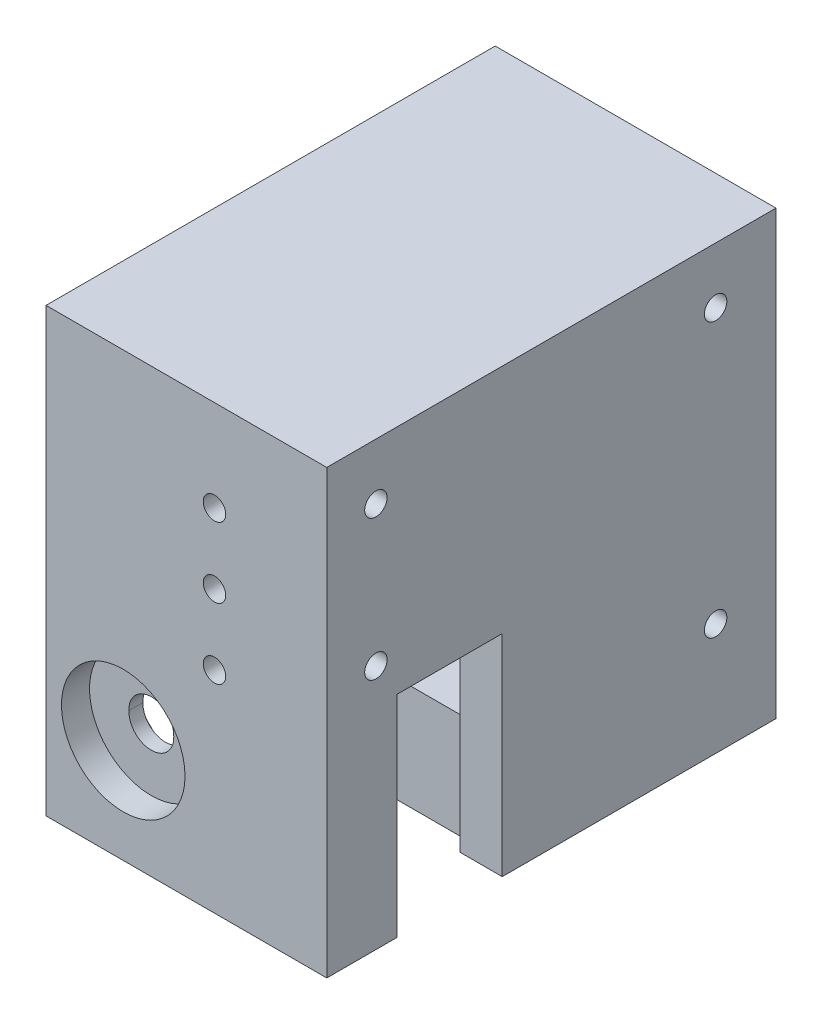
SolidWorks part; units mm, degrees
ref_plane "Front Plane" through (0, 0, 0) normal (0, 0, 1) x (1, 0, 0)
ref_plane "Top Plane" through (0, 0, 0) normal (0, 1, 0) x (1, 0, 0)
ref_plane "Right Plane" through (0, 0, 0) normal (1, 0, 0) x (0, 0, -1)
sketch "Sketch1" plane through (0, 0, 0) normal (0, 0, 1) x (1, 0, 0)
  line L1 (-1.5468, -4.5791) -> (49.2532, -4.5791)
  line L2 (-1.5468, -4.5791) -> (-1.5468, -80.7791)
  line L3 (-1.5468, -80.7791) -> (49.2532, -80.7791)
  line L4 (49.2532, -4.5791) -> (49.2532, -80.7791)
  dimension "D1" = 50.8
  dimension "D2" = 76.2
extrude "Boss-Extrude1" add sketch "Sketch1" along normal blind 12.7
sketch "Sketch3" plane through (0, 0, 12.7) normal (0, 0, 1) x (1, 0, 0)
  line L0 (49.2532, -80.7791) -> (49.2532, -4.5791) construction
  line L1 (49.2532, -4.5791) -> (-1.5468, -4.5791) construction
  line L2 (28.9332, -4.5791) -> (28.9332, -80.7791) construction
  line L4 (-1.5468, -80.7791) -> (49.2532, -80.7791) construction
  circle A0 centre (28.9332, -42.6791) radius 2.032
  circle A1 centre (28.9332, -29.9791) radius 2.032
  circle A2 centre (28.9332, -17.2791) radius 2.032
  dimension "D1" = 12.7
  dimension "D2" = 4.064
  dimension "D3" = 4.064
  dimension "D4" = 4.064
  dimension "D9" = 12.7
  dimension "D5" = 0
  dimension "D6" = 12.7
  dimension "D7" = 20.32
  dimension "D8" = 0
extrude "Cut-Extrude1" cut sketch "Sketch3" against normal blind 12.7
sketch "Sketch4" plane through (0, 0, 12.7) normal (0, 0, 1) x (1, 0, 0)
  circle A1 centre (12.4232, -61.9814) radius 4.064
  circle A4 centre (28.9332, -42.6791) radius 2.032 construction
  dimension "D1" = 25.4
  dimension "D2" = 8.128
  dimension "D3" = 16.51
sketch "Sketch17" plane through (0, 0, 0) normal (0, 0, -1) x (-1, 0, 0)
  line L0 (1.5468, -80.7791) -> (-49.2532, -80.7791) construction
  line L1 (-49.2532, -4.5791) -> (-41.6332, -4.5791)
  line L2 (-49.2532, -4.5791) -> (-49.2532, -80.7791)
  line L3 (-49.2532, -80.7791) -> (-41.6332, -80.7791)
  line L4 (-41.6332, -4.5791) -> (-41.6332, -80.7791)
  dimension "D1" = 7.62
extrude "Boss-Extrude13" add sketch "Sketch17" along normal blind 68.58
sketch "Sketch18" plane through (41.6332, 0, 0) normal (-1, 0, 0) x (0, 0, 1)
  line L1 (-68.58, -80.7791) -> (-64.77, -80.7791)
  line L2 (-68.58, -80.7791) -> (-68.58, -61.7291)
  line L3 (-68.58, -61.7291) -> (-64.77, -61.7291)
  line L4 (-64.77, -80.7791) -> (-64.77, -61.7291)
  dimension "D1" = 19.05
  dimension "D2" = 3.81
extrude "Boss-Extrude14" add sketch "Sketch18" along normal blind 43.18
sketch "Sketch19" plane through (41.6332, 0, 0) normal (-1, 0, 0) x (0, 0, 1)
  line L0 (-64.77, -80.7791) -> (0, -80.7791) construction
  line L1 (-21.59, -80.7791) -> (-50.8, -80.7791)
  line L2 (-21.59, -80.7791) -> (-21.59, -61.7291)
  line L3 (-21.59, -61.7291) -> (-50.8, -61.7291)
  line L4 (-50.8, -80.7791) -> (-50.8, -61.7291)
  line L5 (-64.77, -80.7791) -> (-64.77, -61.7291) construction
  dimension "D1" = 13.97
  dimension "D2" = 29.21
  dimension "D3" = 19.05
extrude "Boss-Extrude15" add sketch "Sketch19" along normal blind 43.18
extrude "Cut-Extrude5" cut sketch "Sketch4" against normal through all contours A1
sketch "Sketch21" plane through (0, 0, 0) normal (0, 0, -1) x (-1, 0, 0)
  circle A0 centre (-12.4232, -61.9814) radius 11.176
  circle A1 centre (-12.4232, -61.9814) radius 4.064
  dimension "D1" = 22.352
  dimension "D2" = 8.128
extrude "Cut-Extrude6" cut sketch "Sketch21" against normal blind 5.08
sketch "Sketch22" plane through (0, 0, 12.7) normal (0, 0, 1) x (1, 0, 0)
  circle A0 centre (12.4232, -61.9814) radius 11.176
  circle A1 centre (12.4232, -61.9814) radius 4.064
  dimension "D1" = 22.352
  dimension "D2" = 8.128
extrude "Cut-Extrude7" cut sketch "Sketch22" against normal blind 5.08
sketch "Sketch23" plane through (41.6332, 0, 0) normal (-1, 0, 0) x (0, 0, 1)
  line L1 (0, -80.7791) -> (-19.05, -80.7791)
  line L2 (0, -80.7791) -> (0, -42.6791)
  line L3 (0, -42.6791) -> (-19.05, -42.6791)
  line L4 (-19.05, -80.7791) -> (-19.05, -42.6791)
  dimension "D1" = 38.1
  dimension "D2" = 19.05
extrude "Cut-Extrude8" cut sketch "Sketch23" against normal through all
sketch "Sketch24" plane through (0, -80.7791, 0) normal (0, -1, 0) x (1, 0, 0)
  line L0 (49.2532, -19.05) -> (49.2532, -68.58) construction
  line L1 (0.9932, -24.0843) -> (45.4432, -24.0843)
  line L2 (0.9932, -24.0843) -> (0.9932, -49.5327)
  line L3 (0.9932, -49.5327) -> (45.4432, -49.5327)
  line L4 (45.4432, -24.0843) -> (45.4432, -49.5327)
  dimension "D1" = 3.81
  dimension "D2" = 44.45
extrude "Cut-Extrude9" cut sketch "Sketch24" against normal blind 7.62
sketch "Sketch26" plane through (0, -61.7291, 0) normal (0, 1, 0) x (1, 0, 0)
  line L8 (16.4793, 21.59) -> (41.6332, 21.59) construction
  line L9 (-1.5468, 68.58) -> (16.9952, 68.58)
  line L10 (-1.5468, 68.58) -> (-1.5468, 21.59)
  line L11 (-1.5468, 21.59) -> (16.9952, 21.59)
  line L12 (16.9952, 68.58) -> (16.9952, 21.59)
  line L13 (41.6332, 68.58) -> (41.6332, 0) construction
  dimension "D1" = 24.638
extrude "Boss-Extrude16" add sketch "Sketch26" along normal blind 57.15
sketch "Sketch28" plane through (0, -4.5791, 0) normal (0, 1, 0) x (1, 0, 0)
  line L5 (-1.5468, 68.58) -> (49.2532, 68.58)
  line L6 (-1.5468, 68.58) -> (-1.5468, -12.7)
  line L7 (-1.5468, -12.7) -> (49.2532, -12.7)
  line L8 (49.2532, 68.58) -> (49.2532, -12.7)
extrude "Boss-Extrude18" add sketch "Sketch28" along normal blind 3.81
sketch "Sketch32" plane through (49.2532, 0, 0) normal (1, 0, 0) x (0, 0, -1)
  line L0 (68.58, -0.7691) -> (68.58, -80.7791) construction
  line L1 (19.05, -80.7791) -> (68.58, -80.7791) construction
  line L4 (-12.7, -0.7691) -> (68.58, -0.7691) construction
  line L6 (-12.7, -80.7791) -> (-12.7, -0.7691) construction
  circle A0 centre (-3.81, -36.3291) radius 2.032
  circle A1 centre (57.785, -10.9291) radius 2.032
  circle A2 centre (57.785, -60.4591) radius 2.032
  circle A3 centre (-3.81, -10.9291) radius 2.032
  dimension "D1" = 4.064
  dimension "D2" = 4.064
  dimension "D3" = 4.064
  dimension "D4" = 4.064
  dimension "D5" = 10.795
  dimension "D6" = 20.32
  dimension "D7" = 10.795
  dimension "D9" = 8.89
  dimension "D10" = 25.4
  dimension "D12" = 0
  dimension "D8" = 10.16
  dimension "D11" = 8.89
sketch "Sketch35" plane through (0, 0, 12.7) normal (0, 0, 1) x (1, 0, 0)
  line L0 (8.367, -61.7291) -> (16.4793, -61.7291) construction
  circle A0 centre (12.4232, -61.7291) radius 4.064
  dimension "D1" = 8.128
extrude "Cut-Extrude10" cut sketch "Sketch35" against normal through all
extrude "Cut-Extrude12" cut sketch "Sketch32" against normal blind 9.525 contours A0 | A3
sketch "Sketch37" plane through (49.2532, 0, 0) normal (1, 0, 0) x (0, 0, -1)
  line L1 (68.58, -0.7691) -> (68.58, -80.7791) construction
  line L2 (-12.7, -0.7691) -> (68.58, -0.7691) construction
  line L3 (19.05, -80.7791) -> (68.58, -80.7791) construction
  circle A0 centre (57.658, -10.9291) radius 2.032
  circle A1 centre (57.658, -60.4591) radius 2.032
  dimension "D1" = 4.064
  dimension "D2" = 10.922
  dimension "D4" = 4.064
  dimension "D5" = 20.32
  dimension "D6" = 10.922
  dimension "D3" = 10.16
sketch "Sketch41" plane through (41.6332, 0, 0) normal (-1, 0, 0) x (0, 0, 1)
  circle A0 centre (-57.658, -10.9291) radius 2.032
  circle A1 centre (-57.658, -60.4591) radius 2.032
  point P0 (-57.658, -10.9291)
  point P3 (-57.658, -60.4591)
extrude "Cut-Extrude14" cut sketch "Sketch41" against normal blind 9.525
sketch "Sketch43" plane through (41.6332, 0, 0) normal (-1, 0, 0) x (0, 0, 1)
  circle A0 centre (-57.658, -10.9291) radius 3.9687
  circle A1 centre (-57.658, -60.4591) radius 3.9687
  dimension "D1" = 7.9375
  dimension "D2" = 7.9375
extrude "Cut-Extrude15" cut sketch "Sketch43" against normal blind 4.7625
